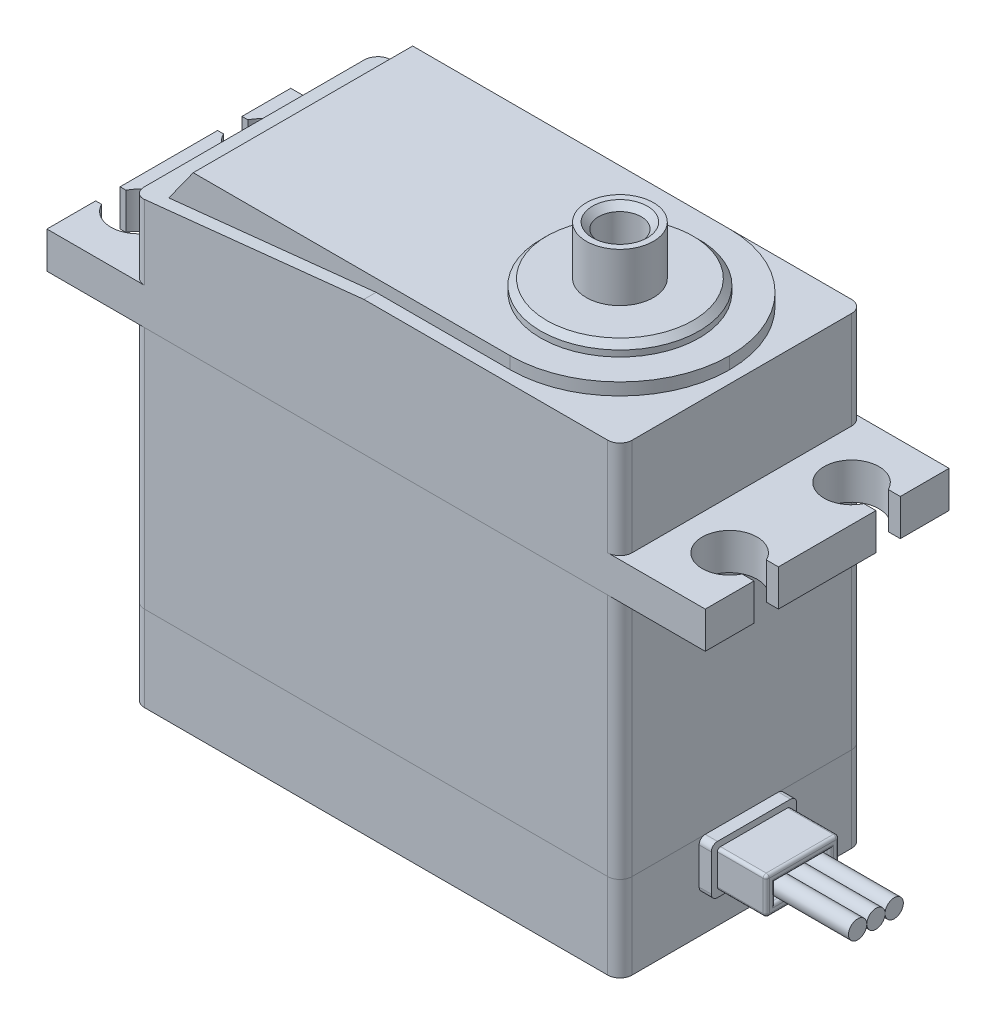
SolidWorks part; units mm, degrees
ref_plane "Front Plane" through (0, 0, 0) normal (0, 0, 1) x (1, 0, 0)
ref_plane "Top Plane" through (0, 0, 0) normal (0, 1, 0) x (1, 0, 0)
ref_plane "Right Plane" through (0, 0, 0) normal (1, 0, 0) x (0, 0, -1)
sketch "Sketch1" plane through (0, 0, 0) normal (0, 1, 0) x (1, 0, 0)
  line L0 (0, 10) -> (0, -10) construction
  line L1 (-20, 10) -> (20, 10)
  line L2 (-20, 10) -> (-20, -10)
  line L3 (-20, -10) -> (20, -10)
  line L4 (20, 10) -> (20, -10)
  point P6 (0, 0)
  dimension "D1" = 40
  dimension "D2" = 20
extrude "Boss-Extrude1" add sketch "Sketch1" along normal blind 7
sketch "Sketch2" plane through (0, 7, 0) normal (0, 1, 0) x (1, 0, 0)
  line L1 (-20, 10) -> (20, 10)
  line L2 (-20, 10) -> (-20, -10)
  line L3 (-20, -10) -> (20, -10)
  line L4 (20, 10) -> (20, -10)
extrude "Boss-Extrude2" add sketch "Sketch2" along normal blind 20 separate body
sketch "Sketch3" plane through (0, 0, 10) normal (0, 0, 1) x (1, 0, 0)
  line L0 (-27, 27) -> (27, 27)
  line L1 (27, 27) -> (27, 30)
  line L2 (27, 30) -> (20, 30)
  line L3 (20, 30) -> (20, 38)
  line L5 (-20, 36) -> (-20, 30)
  line L6 (-20, 30) -> (-27, 30)
  line L7 (-27, 30) -> (-27, 27)
  line L8 (-20, 27) -> (20, 27) construction
  line L9 (20, 38) -> (-1, 38)
  line L10 (-1, 38) -> (-20, 36)
  point P7 (0, 27)
  dimension "D1" = 54
  dimension "D2" = 7
  dimension "D3" = 3
  dimension "D4" = 8
  dimension "D5" = 6
  dimension "D6" = 21
extrude "Boss-Extrude3" add sketch "Sketch3" against normal up to surface (20 mm away) separate body up to face at (0, 17, -10)
sketch "Sketch4" plane through (0, 0, 0) normal (0, 0, 1) x (1, 0, 0)
  line L0 (-18, 36.2105) -> (-16, 39)
  line L1 (-1, 38) -> (-20, 36) construction
  line L2 (-16, 39) -> (19, 39)
  line L3 (19, 39) -> (19, 38)
  line L4 (20, 38) -> (-1, 38) construction
  line L5 (19, 38) -> (-1, 38)
  line L6 (-1, 38) -> (-18, 36.2105)
  line L7 (20, 30) -> (20, 38) construction
  line L9 (-20, 36) -> (-20, 30) construction
  dimension "D1" = 2
  dimension "D2" = 1
  dimension "D3" = 1
  dimension "D4" = 4
extrude "Boss-Extrude4" add sketch "Sketch4" along normal mid plane 18
sketch "Sketch5" plane through (0, 39, 0) normal (0, 1, 0) x (1, 0, 0)
  line L0 (20, 10) -> (20, -10) construction
  circle A0 centre (10, 0) radius 6.5
  point P0 (10, 0)
  dimension "D2" = 13
  dimension "D1" = 10
extrude "Boss-Extrude5" add sketch "Sketch5" along normal blind 1
chamfer "Chamfer1" distance 0.5 angle 45 1 edges at (10, 40, 6.5)
fillet "Fillet1" radius 9 2 edges at (19, 38.5, -9) (19, 38.5, 9)
fillet "Fillet2" radius 1 4 edges at (-20, 3.5, 10) (-20, 3.5, -10) (20, 3.5, -10) (20, 3.5, 10)
fillet "Fillet3" radius 1 4 edges at (20, 17, 10) (20, 17, -10) (-20, 17, -10) (-20, 17, 10)
fillet "Fillet4" radius 1 4 edges at (-20, 33, 10) (-20, 33, -10) (20, 34, -10) (20, 34, 10)
sketch "Sketch6" plane through (0, 30, 0) normal (0, 1, 0) x (1, 0, 0)
  line L0 (-24.5, 5) -> (-24.5, -5) construction
  line L1 (27, 10) -> (27, -10) construction
  line L2 (-27, 0) -> (-24.5, 0) construction
  line L3 (24, 5) -> (24, -5) construction
  line L4 (24, 0) -> (27, 0) construction
  line L5 (-27, 6) -> (-26.5156, 6)
  line L6 (-27, 10) -> (-27, -10) construction
  line L7 (-27, 6) -> (-27, 4)
  line L8 (-27, 4) -> (-26.5156, 4)
  line L9 (-26.5156, -4) -> (-27, -4)
  line L10 (-27, -4) -> (-27, -6)
  line L11 (-27, -6) -> (-26.5156, -6)
  line L12 (26.0156, 6) -> (27, 6)
  line L13 (27, 6) -> (27, 4)
  line L14 (27, 4) -> (26.0156, 4)
  line L15 (26.0156, -4) -> (27, -4)
  line L16 (27, -4) -> (27, -6)
  line L17 (27, -6) -> (26.0156, -6)
  arc A0 (-26.5156, 4) -> (-26.5156, 6) centre (-24.5, 5) ccw
  arc A1 (-26.5156, -6) -> (-26.5156, -4) centre (-24.5, -5) ccw
  arc A2 (26.0156, 6) -> (26.0156, 4) centre (24, 5) ccw
  arc A3 (26.0156, -4) -> (26.0156, -6) centre (24, -5) ccw
  dimension "D1" = 2
  dimension "D2" = 2.25
  dimension "D3" = 2.5
  dimension "D4" = 3
  dimension "D5" = 10
extrude "Cut-Extrude1" cut sketch "Sketch6" against normal up to next (3 mm away)
sketch "Sketch7" plane through (0, 40, 0) normal (0, 1, 0) x (1, 0, 0)
  circle A0 centre (10, 0) radius 2.75
  circle A1 centre (10, 0) radius 1.75
  dimension "D1" = 3.5
extrude "Boss-Extrude6" add sketch "Sketch7" along normal blind 4 separate body
chamfer "Chamfer2" distance 0.5 angle 45 1 edges at (10, 44, 1.75)
sketch "Sketch8" plane through (20, 0, 0) normal (1, 0, 0) x (0, 0, -1)
  line L0 (-9, 7) -> (9, 7) construction
  line L1 (-3.5, 7) -> (3.5, 7)
  line L2 (-3.5, 7) -> (-3.5, 3)
  line L3 (-3.5, 3) -> (3.5, 3)
  line L4 (3.5, 7) -> (3.5, 3)
  line L5 (-9, 7) -> (9, 7) construction
  point P8 (0, 7)
  dimension "D1" = 7
  dimension "D2" = 4
extrude "Boss-Extrude7" add sketch "Sketch8" along normal blind 1 separate body
sketch "Sketch9" plane through (21, 0, 0) normal (1, 0, 0) x (0, 0, -1)
  line L0 (0, 7) -> (0, 6.5) construction
  line L1 (-3, 6.5) -> (3, 6.5)
  line L2 (-3, 6.5) -> (-3, 3.5)
  line L3 (-3, 3.5) -> (3, 3.5)
  line L4 (3, 6.5) -> (3, 3.5)
  line L5 (3.5, 7) -> (-3.5, 7) construction
  line L6 (0, 3.5) -> (0, 3) construction
  line L7 (-3.5, 3) -> (3.5, 3) construction
  dimension "D1" = 6
  dimension "D2" = 3
extrude "Boss-Extrude8" add sketch "Sketch9" along normal blind 4
sketch "Sketch10" plane through (25, 0, 0) normal (1, 0, 0) x (0, 0, -1)
  line L0 (-3, 6.5) -> (-3, 3.5) construction
  line L1 (-2.25, 5.75) -> (2.25, 5.75)
  line L2 (-2.25, 5.75) -> (-2.25, 4.25)
  line L3 (-2.25, 4.25) -> (2.25, 4.25)
  line L4 (2.25, 5.75) -> (2.25, 4.25)
  line L5 (3, 3.5) -> (3, 6.5) construction
  line L6 (3, 6.5) -> (-3, 6.5) construction
  line L7 (-3, 3.5) -> (3, 3.5) construction
  dimension "D1" = 0.75
  dimension "D2" = 0.75
  dimension "D3" = 0.75
  dimension "D4" = 0.75
extrude "Cut-Extrude2" cut sketch "Sketch10" against normal blind 4
sketch "Sketch11" plane through (21, 0, 0) normal (1, 0, 0) x (0, 0, -1)
  line L0 (-2.25, 5) -> (2.25, 5) construction
  line L1 (-2.25, 5.75) -> (-2.25, 4.25) construction
  line L2 (2.25, 4.25) -> (2.25, 5.75) construction
  circle A0 centre (0, 5) radius 0.75
  dimension "D1" = 1.5
extrude "Boss-Extrude9" add sketch "Sketch11" along normal blind 10 separate body
sketch "Sketch12" plane through (21, 0, 0) normal (1, 0, 0) x (0, 0, -1)
  line L0 (1.5, 5) -> (2.25, 5) construction
  line L1 (2.25, 4.25) -> (2.25, 5.75) construction
  circle A0 centre (1.5, 5) radius 0.75
  dimension "D1" = 1.5
  dimension "D2" = 0.75
extrude "Boss-Extrude10" add sketch "Sketch12" along normal blind 10 separate body
sketch "Sketch13" plane through (21, 0, 0) normal (1, 0, 0) x (0, 0, -1)
  line L1 (-2.25, 5) -> (-1.5, 5) construction
  line L2 (-2.25, 5.75) -> (-2.25, 4.25) construction
  circle A0 centre (-1.5, 5) radius 0.75
  dimension "D1" = 1.5
  dimension "D2" = 0.75
extrude "Boss-Extrude11" add sketch "Sketch13" along normal blind 10 separate body
fillet "Fillet5" radius 0.5 4 edges at (20.5, 7, 3.5) (20.5, 3, 3.5) (20.5, 3, -3.5) (20.5, 7, -3.5)
fillet "Fillet6" radius 0.25 4 edges at (23, 6.5, 3) (23, 6.5, -3) (23, 3.5, -3) (23, 3.5, 3)
fillet "Fillet7" radius 0.25 12 edges at (25, 5, 2.25) (25, 4.25, 0) (25, 5, -2.25) (25, 5.75, 0) (25, 6.4268, -2.9268) (25, 3.5732, -2.9268) (25, 3.5732, 2.9268) (25, 6.4268, 2.9268) (25, 3.5, 0) (25, 5, 3) (25, 5, -3) (25, 6.5, 0)
